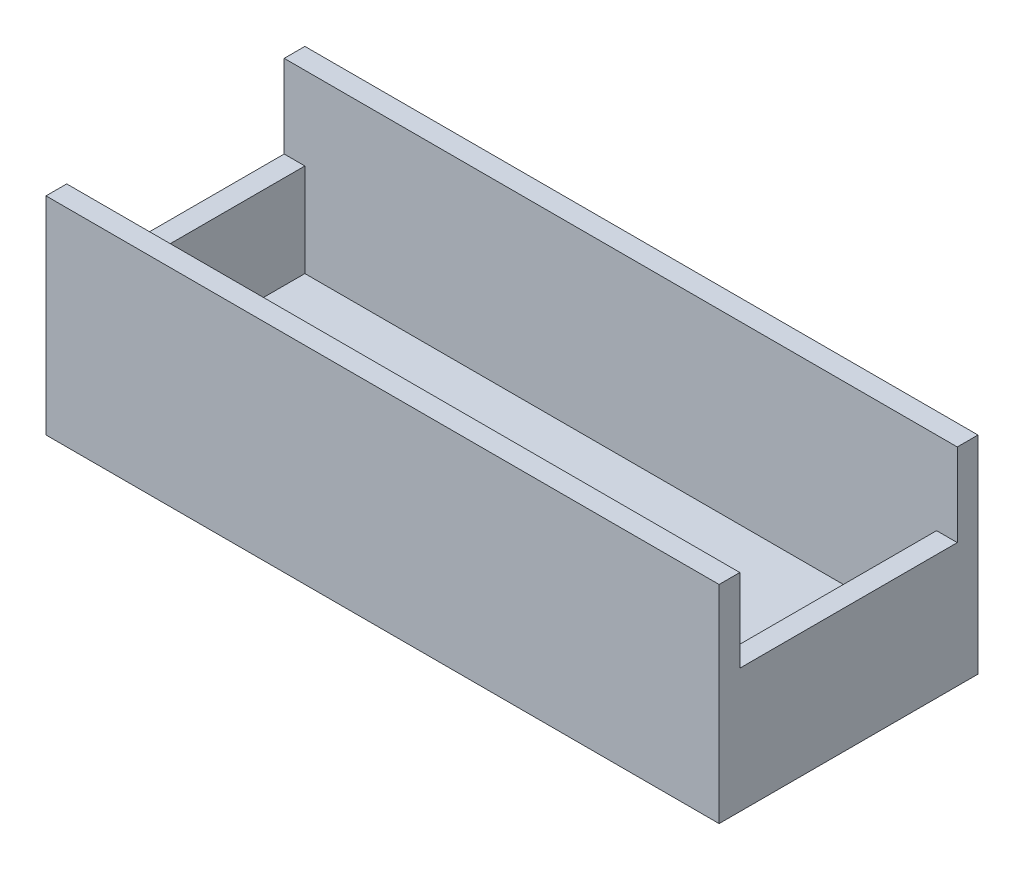
SolidWorks part; units mm, degrees
ref_plane "Front Plane" through (0, 0, 0) normal (0, 0, 1) x (1, 0, 0)
ref_plane "Top Plane" through (0, 0, 0) normal (0, 1, 0) x (1, 0, 0)
ref_plane "Right Plane" through (0, 0, 0) normal (1, 0, 0) x (0, 0, -1)
sketch "Sketch1" plane through (0, 0, 0) normal (0, 1, 0) x (1, 0, 0)
  line L5 (0, 0) -> (65, 0)
  line L6 (0, 0) -> (0, -25)
  line L7 (0, -25) -> (65, -25)
  line L8 (65, 0) -> (65, -25)
  dimension "D1" = 65
  dimension "D2" = 25
extrude "Boss-Extrude1" add sketch "Sketch1" along normal blind 3
sketch "Sketch2" plane through (0, 3, 0) normal (0, 1, 0) x (1, 0, 0)
  line L0 (65, 0) -> (0, 0) construction
  line L1 (2, -2) -> (63, -2)
  line L2 (2, -2) -> (2, -23)
  line L3 (2, -23) -> (63, -23)
  line L4 (63, -2) -> (63, -23)
  line L5 (0, -25) -> (65, -25) construction
  line L6 (65, -25) -> (65, 0) construction
  line L7 (0, 0) -> (0, -25) construction
  line L8 (2, -2) -> (0, -2)
  line L9 (2, -23) -> (0, -23)
  line L10 (63, -23) -> (65, -23)
  line L11 (63, -2) -> (65, -2)
  line L13 (0, 0) -> (65, 0)
  line L14 (0, 0) -> (0, -25)
  line L15 (0, -25) -> (65, -25)
  line L16 (65, 0) -> (65, -25)
  line M5 (0, 0) -> (0, -25)
  line M6 (0, -25) -> (65, -25)
  line M7 (65, -25) -> (65, 0)
  line M8 (65, 0) -> (0, 0)
  dimension "D1" = 2
  dimension "D2" = 2
  dimension "D3" = 2
  dimension "D4" = 2
extrude "Boss-Extrude2" add sketch "Sketch2" along normal blind 17 contours L10 L3 L9 M5 M6 M7 | L1 L11 L8 M7 M8 M5 region at (32.5, 3, 1) region at (32.5, 3, 24)
extrude "Boss-Extrude3" add sketch "Sketch2<3>" along normal blind 9 contours L9 L2 L8 M5 | L11 L4 L10 M7 region at (1, 3, 12.5) region at (64, 3, 12.5)
sketch "Sketch2<3>" plane through (0, 3, 0) normal (0, 1, 0) x (1, 0, 0) same geometry as "Sketch2"
